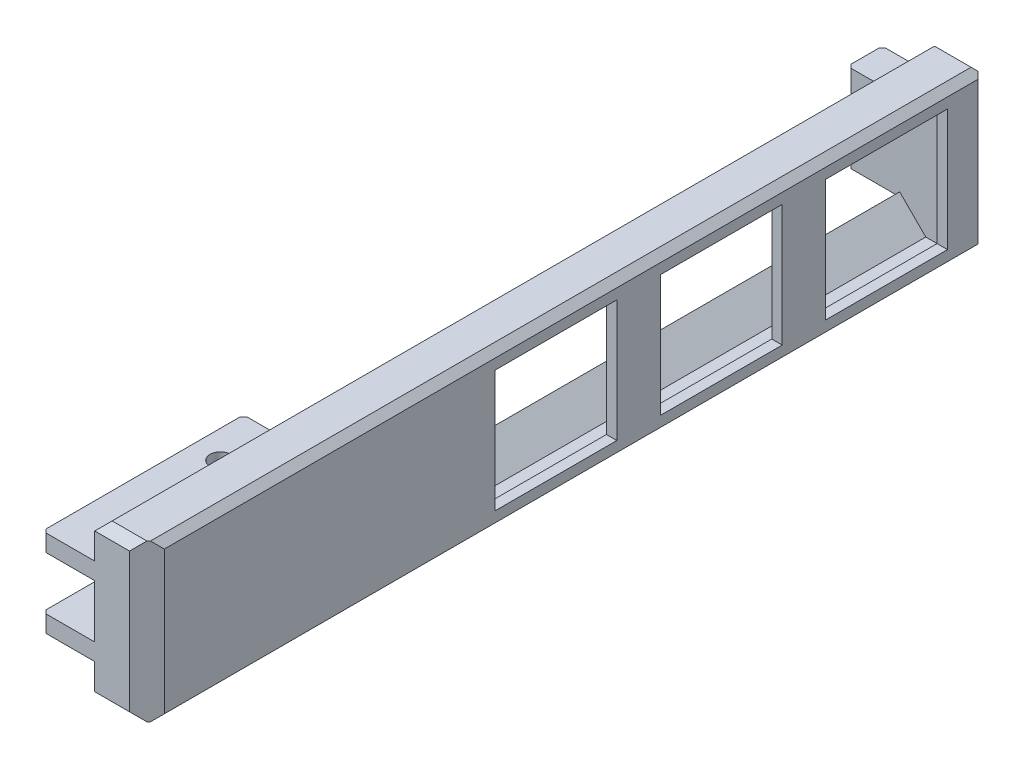
SolidWorks part; units mm, degrees
ref_plane "前视基准面" through (0, 0, 0) normal (0, 0, 1) x (1, 0, 0)
ref_plane "上视基准面" through (0, 0, 0) normal (0, 1, 0) x (1, 0, 0)
ref_plane "右视基准面" through (0, 0, 0) normal (1, 0, 0) x (0, 0, -1)
sketch "草图2" plane through (0, 0, 0) normal (1, 0, 0) x (0, 0, -1)
  line L0 (-24.1958, 9) -> (135.844, 9) construction
  line L1 (0, 0) -> (96.5, 0)
  line L2 (0, 0) -> (0, 18)
  line L3 (0, 18) -> (96.5, 18)
  line L4 (96.5, 0) -> (96.5, 18)
  dimension "D1" = 18
  dimension "D2" = 96.5
extrude "凸台-拉伸1" add sketch "草图2" along normal blind 12
sketch "草图3" plane through (12, 0, 0) normal (1, 0, 0) x (0, 0, -1)
  line L0 (0, 0) -> (96.5, 0) construction
  line L1 (96.5, 18) -> (0, 18) construction
  line L2 (0, 0) -> (96.5, 0) construction
  line L3 (96.5, 18) -> (0, 18) construction
  line L4 (-10.5677, 9) -> (109.3221, 9) construction
  line L5 (96.5, 0) -> (96.5, 18) construction
  line L6 (78, 16) -> (92, 16)
  line L7 (78, 16) -> (78, 2)
  line L8 (78, 2) -> (92, 2)
  line L9 (92, 16) -> (92, 2)
  line L10 (78, 16) -> (92, 2) construction
  line L11 (78, 2) -> (92, 16) construction
  line L12 (59, 16) -> (73, 16)
  line L13 (59, 16) -> (59, 2)
  line L14 (59, 2) -> (73, 2)
  line L15 (73, 16) -> (73, 2)
  line L16 (59, 16) -> (73, 2) construction
  line L17 (59, 2) -> (73, 16) construction
  line L18 (40, 16) -> (54, 16)
  line L19 (40, 16) -> (40, 2)
  line L20 (40, 2) -> (54, 2)
  line L21 (54, 16) -> (54, 2)
  line L22 (40, 16) -> (54, 2) construction
  line L23 (40, 2) -> (54, 16) construction
  point P6 (85, 9)
  point P11 (66, 9)
  point P16 (47, 9)
  dimension "D1" = 14
  dimension "D2" = 19
  dimension "D3" = 19
  dimension "D4" = 4.5
extrude "切除-拉伸1" cut sketch "草图3" against normal blind 1.2
sketch "草图4" plane through (10.8, 0, 0) normal (1, 0, 0) x (0, 0, -1)
  line L0 (96.5, 0) -> (96.5, 18) construction
  line L1 (36.5, 16.5) -> (92.5, 16.5)
  line L2 (36.5, 16.5) -> (36.5, 1.5)
  line L3 (36.5, 1.5) -> (92.5, 1.5)
  line L4 (92.5, 16.5) -> (92.5, 1.5)
  line L5 (96.5, 18) -> (0, 18) construction
  line L6 (0, 0) -> (96.5, 0) construction
  dimension "D1" = 4
  dimension "D2" = 1.5
  dimension "D3" = 1.5
  dimension "D4" = 56
extrude "切除-拉伸2" cut sketch "草图4" against normal blind 4.8
chamfer "倒角1" distance 0.3 angle 45 2 edges at (10.8, 1.5, -64.5) (10.8, 16.5, -64.5)
chamfer "倒角2" distance 3 angle 45 2 edges at (6, 1.5, -64.5) (6, 16.5, -64.5)
sketch "草图6" plane through (0, 0, -96.5) normal (0, 0, -1) x (-1, 0, 0)
  line L0 (0, 0) -> (0, 18) construction
  line L1 (0, 12.05) -> (-6, 12.05)
  line L2 (0, 12.05) -> (0, 5.95)
  line L3 (0, 5.95) -> (-6, 5.95)
  line L4 (-6, 12.05) -> (-6, 5.95)
  line L5 (5.6103, 9) -> (-10.6258, 9) construction
  line L6 (0, 18) -> (-6, 18)
  line L7 (0, 18) -> (0, 14)
  line L8 (0, 14) -> (-6, 14)
  line L9 (-6, 18) -> (-6, 14)
  line L10 (0, 0) -> (-6, 0)
  line L11 (0, 0) -> (0, 4)
  line L12 (0, 4) -> (-6, 4)
  line L13 (-6, 0) -> (-6, 4)
  line M13 (0, 0) -> (0, 18)
  line M14 (0, 18) -> (-12, 18)
  line M16 (-12, 0) -> (0, 0)
  dimension "D1" = 6.1
  dimension "D2" = 6
  dimension "D3" = 4
extrude "切除-拉伸3" cut sketch "草图6" against normal through all contours L9 L8 M14 M13 | L13 L12 M16 M13 region at (3, 2, -96.5) region at (3, 16, -96.5)
extrude "切除-拉伸5" cut sketch "草图6<4>" against normal through all from offset 4 contours L3 L4 L1 L2 offset against normal yes
sketch "草图6<4>" plane through (0, 0, -96.5) normal (0, 0, -1) x (-1, 0, 0) same geometry as "草图6"
sketch "草图7" plane through (0, 0, 0) normal (-1, 0, 0) x (0, 0, 1)
  line L0 (-88.9, 14) -> (-7.6, 14) construction
  line L1 (-92.5, 14) -> (-23.1, 14)
  line L2 (-92.5, 14) -> (-92.5, 4)
  line L3 (-92.5, 4) -> (-23.1, 4)
  line L4 (-23.1, 14) -> (-23.1, 4)
  line L5 (-7.6, 4) -> (-88.9, 4) construction
  line L8 (0, 14) -> (0, 12.05) construction
  line L10 (-92.5, 1.8) -> (-92.5, 16.2) construction
  dimension "D1" = 23.1
extrude "切除-拉伸4" cut sketch "草图7" against normal up to surface (6 mm away) up to face at (6, 16, -48.25)
chamfer "倒角3" distance 0.4 angle 45 8 edges at (0, 4.975, 0) (0, 13.025, 0) (0, 4.975, -23.1) (0, 13.025, -23.1) (0, 9, -92.5) (0, 9, -96.5) (3, 5.95, -23.1) (3, 12.05, -23.1)
sketch "草图8" plane through (0, 14, 0) normal (0, 1, 0) x (1, 0, 0)
  circle A0 centre (3.2, 17.25) radius 1.2 construction
  circle A1 centre (3.2, 17.25) radius 1.2
extrude "切除-拉伸6" cut sketch "草图8" against normal through all
sketch "草图9" plane through (0, 0, -96.5) normal (0, 0, -1) x (-1, 0, 0)
  line L0 (-14.8901, 9) -> (2.9934, 9) construction
  line L1 (-0.4, 14) -> (-6, 14) construction
  line L2 (-0.4, 4) -> (-6, 4) construction
  line L3 (0, 14) -> (0, 4) construction
  circle A0 centre (-3, 9) radius 2.05
  circle A1 centre (-3, 9) radius 1.2
  dimension "D1" = 3
  dimension "D2" = 4.1
  dimension "D3" = 2.4
extrude "切除-拉伸7" cut sketch "草图9" against normal blind 2 contours A0
extrude "切除-拉伸8" cut sketch "草图9<3>" against normal through all contours A1
sketch "草图9<3>" plane through (0, 0, -96.5) normal (0, 0, -1) x (-1, 0, 0) same geometry as "草图9"
chamfer "倒角4" distance 1 angle 45 5 edges at (9, 0, -96.5) (12, 9, -96.5) (9, 18, -96.5) (6, 0, -48.25) (6, 18, -48.25)
chamfer "倒角5" distance 2 angle 45 1 edges at (12, 9, 0)
chamfer "倒角6" distance 0.8 angle 45 2 edges at (12, 0, -48.75) (12, 18, -48.75)
chamfer "倒角7" distance 1 angle 45 2 edges at (8.5, 0, 0) (8.5, 18, 0)
